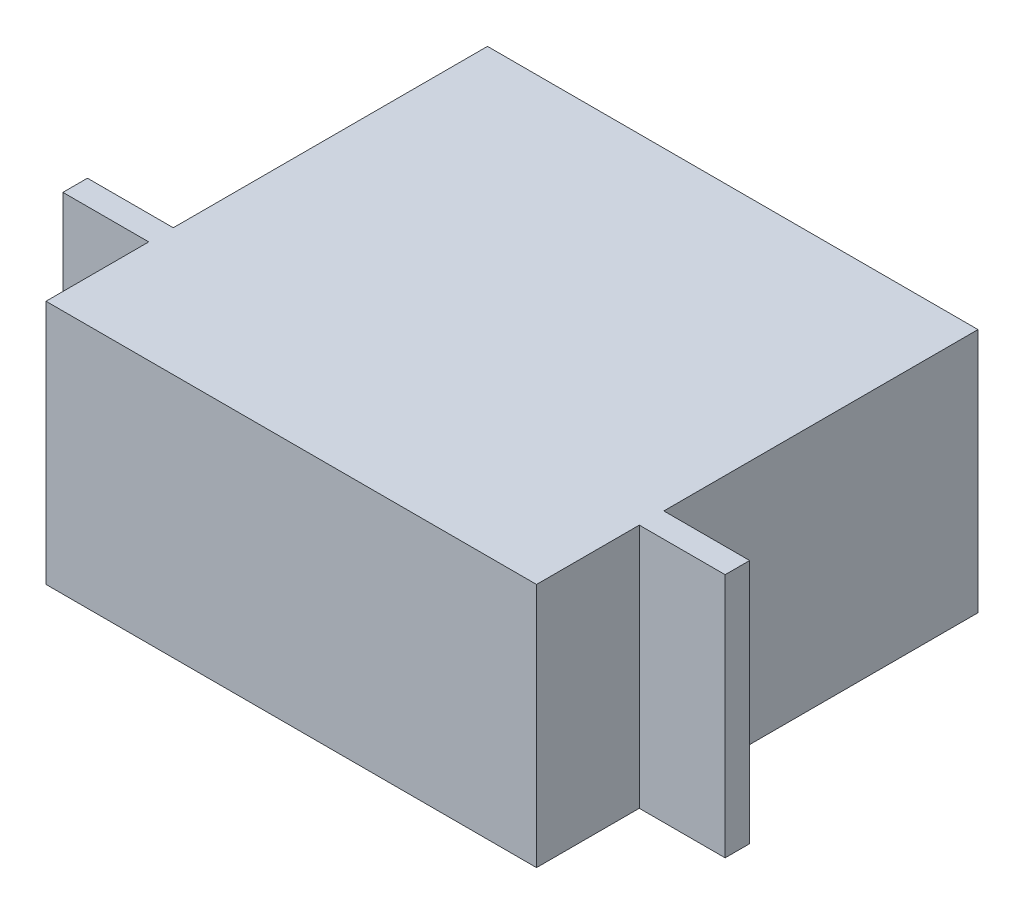
SolidWorks part; units mm, degrees
ref_plane "Front Plane" through (0, 0, 0) normal (0, 0, 1) x (1, 0, 0)
ref_plane "Top Plane" through (0, 0, 0) normal (0, 1, 0) x (1, 0, 0)
ref_plane "Right Plane" through (0, 0, 0) normal (1, 0, 0) x (0, 0, -1)
sketch "Sketch1" plane through (0, 0, 0) normal (0, 1, 0) x (1, 0, 0)
  line L1 (-20, -18) -> (20, -18)
  line L2 (-20, -18) -> (-20, 18)
  line L3 (-20, 18) -> (20, 18)
  line L4 (20, -18) -> (20, 18)
  line L5 (-20, -18) -> (20, 18) construction
  line L6 (-20, 18) -> (20, -18) construction
  point P0 (0, 0)
  dimension "D1" = 40
  dimension "D2" = 36
extrude "Boss-Extrude1" add sketch "Sketch1" along normal mid plane 20
sketch "Sketch2" plane through (0, 0, 0) normal (0, 0, 1) x (1, 0, 0)
  line L0 (-20, -10) -> (20, -10) construction
  line L1 (-20, 10) -> (-27, 10)
  line L2 (-20, 10) -> (-20, -10)
  line L3 (-20, -10) -> (-27, -10)
  line L4 (-27, 10) -> (-27, -10)
  line L5 (20, 10) -> (27, 10)
  line L6 (20, 10) -> (20, -10)
  line L7 (20, -10) -> (27, -10)
  line L8 (27, 10) -> (27, -10)
  dimension "D1" = 7
extrude "Boss-Extrude2" add sketch "Sketch2" along normal blind 2 from offset 7.62
